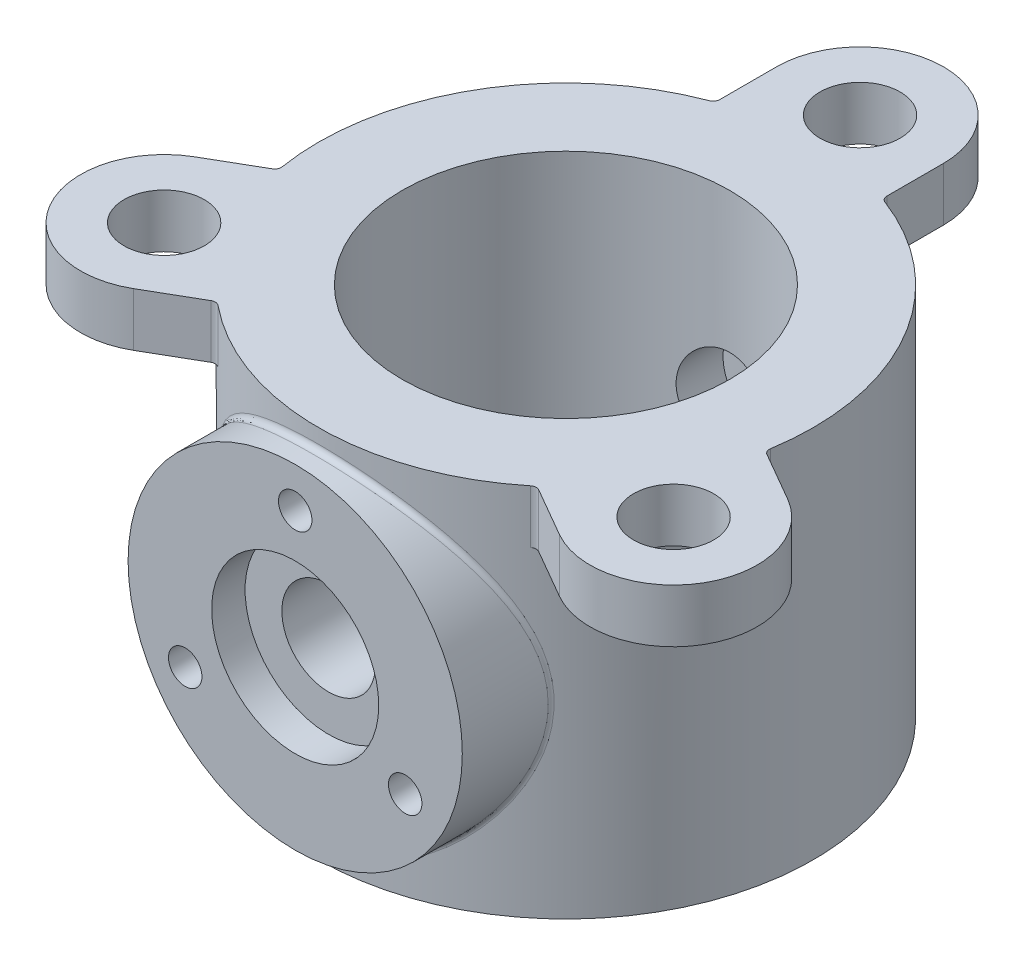
SolidWorks part; units mm, degrees
ref_plane "Front Plane" through (0, 0, 0) normal (0, 0, 1) x (1, 0, 0)
ref_plane "Top Plane" through (0, 0, 0) normal (0, 1, 0) x (1, 0, 0)
ref_plane "Right Plane" through (0, 0, 0) normal (1, 0, 0) x (0, 0, -1)
sketch "Sketch2" plane through (0, 0, 0) normal (0, 1, 0) x (1, 0, 0)
  line L0 (-12.5, 44) -> (-12.5, 34.8246)
  line L1 (12.5, 44) -> (12.5, 34.8246)
  line L2 (31.8551, -32.8253) -> (23.909, -28.2376)
  line L3 (44.3551, -11.1747) -> (36.409, -6.587)
  line L4 (-44.3551, -11.1747) -> (-36.409, -6.587)
  line L5 (-31.8551, -32.8253) -> (-23.909, -28.2376)
  circle A0 centre (0, 0) radius 24.5
  arc A1 (-12.5, 34.8246) -> (-36.409, -6.587) centre (0, 0) ccw
  arc A8 (-23.909, -28.2376) -> (23.909, -28.2376) centre (0, 0) ccw
  arc A9 (36.409, -6.587) -> (12.5, 34.8246) centre (0, 0) ccw
  circle A10 centre (0, 44) radius 6
  arc A11 (12.5, 44) -> (-12.5, 44) centre (0, 44) ccw
  circle A12 centre (38.1051, -22) radius 6
  arc A13 (31.8551, -32.8253) -> (44.3551, -11.1747) centre (38.1051, -22) ccw
  circle A14 centre (-38.1051, -22) radius 6
  arc A15 (-44.3551, -11.1747) -> (-31.8551, -32.8253) centre (-38.1051, -22) ccw
  point P4 (0, 0)
  point P6 (0, 0)
  point P23 (0, 0)
  point P29 (0, 0)
  dimension "D1" = 49
  dimension "D2" = 74
  dimension "D3" = 3
  dimension "D4" = 12
  dimension "D6" = 44
  dimension "D5" = 12.5
extrude "Boss-Extrude2" add sketch "Sketch2" along normal blind 8
sketch "Sketch3" plane through (0, 0, 0) normal (0, -1, 0) x (1, 0, 0)
  circle A0 centre (0, 0) radius 37
  dimension "D1" = 74
extrude "Boss-Extrude3" add sketch "Sketch3" along normal blind 48
sketch "Sketch4" plane through (0, 0, 0) normal (0, 1, 0) x (1, 0, 0)
  circle A0 centre (0, 0) radius 24.5 construction
  circle A1 centre (0, 0) radius 24.5
extrude "Cut-Extrude1" cut sketch "Sketch4" against normal up to next
ref_plane "Plane1" through (0, 0, 40.5) normal (0, 0, 1) x (1, 0, 0)
sketch "Sketch5" plane through (0, 0, 40.5) normal (0, 0, 1) x (1, 0, 0)
  line L0 (-37, -48) -> (37, -48) construction
  circle A0 centre (0, -20) radius 25
  point P2 (0, 0)
  dimension "D1" = 50
  dimension "D2" = 28
extrude "Boss-Extrude4" add sketch "Sketch5" against normal up to surface (13.2236 mm away) up to face at (0, 4, 0)
hole_wizard "CBORE for M24 Hex Head Bolt1" positions "3DSketch1" profile "Sketch6" counterbore size "M24" standard "ANSI Metric"
sketch3d "3DSketch1"
  circle A0 centre (0, -20, 40.5) radius 25 construction
  point P0 (0, -20, 40.5)
  point P5 (0, -20, 65.5)
sketch "Sketch6" plane through (0, -20, 40.5) normal (1, 0, 0) x (0, -1, 0)
  line L0 (0, 0) -> (0, 71)
  line L1 (0, 71) -> (7, 71)
  line L2 (7, 71) -> (7, 5)
  line L3 (7, 5) -> (12.5, 5)
  line L4 (12.5, 5) -> (12.5, 0)
  line L5 (12.5, 0) -> (0, 0)
  line L10 (0, 71) -> (-7, 71) construction
  line L11 (0, -6.35) -> (0, 107.95) construction
  dimension "Hole Dia." = 14
  dimension "Hole Depth" = 71
  dimension "C'Bore Dia." = 25
  dimension "C'Bore Depth" = 5
  dimension "Drill Angle" = 180
sketch "Sketch7" plane through (0, 0, 40.5) normal (0, 0, 1) x (1, 0, 0)
  circle A0 centre (0, -20) radius 7 construction
  point P0 (0, -1)
  dimension "D1" = 19
hole_wizard "Ø5.0mm Dowel Hole1" positions "3DSketch2" profile "Sketch8" hole size "Ø5.0" standard "ANSI Metric"
sketch3d "3DSketch2"
  point P0 (0, -1, 40.5)
sketch "Sketch8" plane through (0, -1, 40.5) normal (1, 0, 0) x (0, -1, 0)
  line L0 (0, 0) -> (0, 8)
  line L1 (0, 8) -> (2.5, 8)
  line L2 (2.5, 8) -> (2.5, 0)
  line L5 (2.5, 0) -> (0, 0)
  line L10 (0, 8) -> (-2.5, 8) construction
  line L11 (0, -6.35) -> (0, 107.95) construction
  dimension "Hole Dia." = 5
  dimension "Hole Depth" = 8
  dimension "Drill Angle" = 180
pattern_circular "CirPattern1" count 3 over 360 about axis through (0, -20, 40.5) along (0, 0, 1) of "Ø5.0mm Dowel Hole1"
fillet "Fillet1" radius 0.85 1 edges at (-24.7131, -23.7768, 27.5366)
fillet "Fillet2" radius 1 6 edges at (-36.409, 4, 6.587) (-12.5, 4, -34.8246) (12.5, 4, -34.8246) (36.409, 4, 6.587) (23.909, 4, 28.2376) (-23.909, 4, 28.2376)
